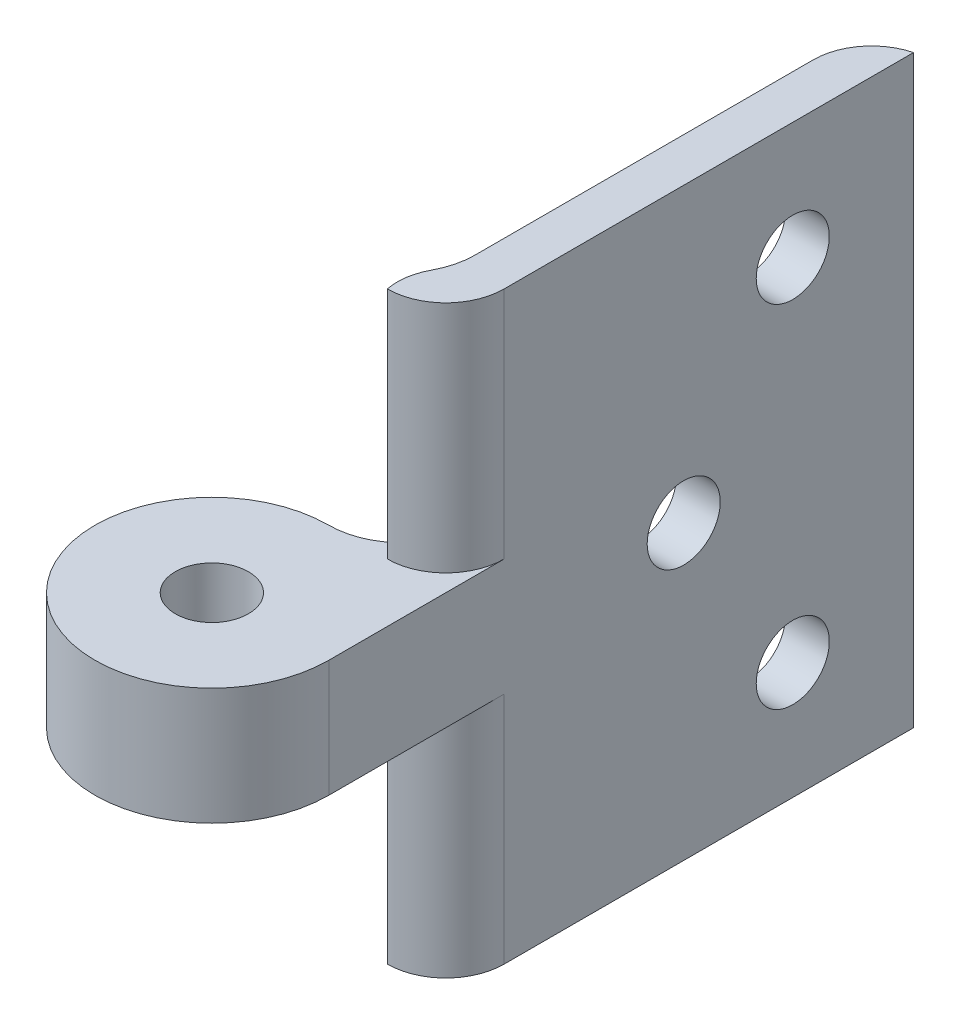
SolidWorks part; units mm, degrees
ref_plane "Front Plane" through (0, 0, 0) normal (0, 0, 1) x (1, 0, 0)
ref_plane "Top Plane" through (0, 0, 0) normal (0, 1, 0) x (1, 0, 0)
ref_plane "Right Plane" through (0, 0, 0) normal (1, 0, 0) x (0, 0, -1)
sketch "Sketch1" plane through (0, 0, 0) normal (0, 1, 0) x (1, 0, 0)
  line L0 (4, 0) -> (4, 20)
  line L1 (2.5, 6.5) -> (2.5, 15.12)
  line L5 (2.5, 15.12) -> (2.5, 20)
  line L6 (2.5, 20) -> (4, 20)
  circle A0 centre (0, 0) radius 1.25
  arc A1 (0, 4) -> (4, 0) centre (0, 0) ccw
  arc A2 (2.5, 6.5) -> (0, 4) centre (0, 6.5) cw
  dimension "D1" = 2.5
  dimension "D2" = 8
  dimension "D4" = 2.5
  dimension "D3" = 20
extrude "Boss-Extrude1" add sketch "Sketch1" along normal blind 20
sketch "Sketch2" plane through (2.5, 0, 0) normal (-1, 0, 0) x (0, 0, 1)
  line L0 (-6.5, 20) -> (-6.5, 0) construction
  circle A0 centre (-12.1392, 10) radius 1.25
  circle A1 centre (-15.8687, 4) radius 1.25
  circle A2 centre (-15.8687, 16) radius 1.25
  point P11 (-6.5, 10)
  dimension "D1" = 2.5
extrude "Cut-Extrude1" cut sketch "Sketch2" against normal through all both and the other way through all
sketch "Sketch3" plane through (0, 0, 0) normal (1, 0, 0) x (0, 0, -1)
  line L0 (4, 20) -> (4, 0) construction
  line L11 (-6, 0) -> (4, 0)
  line L15 (-6, 0) -> (-6, 8)
  line L16 (-6, 8) -> (4, 8)
  line L17 (4, 0) -> (4, 8)
  line L20 (-6, 0) -> (4, 8) construction
  line L21 (-6, 8) -> (4, 0) construction
  line L22 (4, 12) -> (-5.3571, 12)
  line L23 (4, 12) -> (4, 20)
  line L24 (4, 20) -> (-5.3571, 20)
  line L25 (-5.3571, 12) -> (-5.3571, 20)
  line L26 (4, 12) -> (-5.3571, 20) construction
  line L27 (4, 20) -> (-5.3571, 12) construction
  line L28 (-4, 0) -> (4, 0) construction
  line L29 (4, 20) -> (-4, 20) construction
  point P0 (-1.0127, 3.8091)
  point P2 (-0.5182, 16.1371)
  dimension "D1" = 4
  dimension "D2" = 8
  dimension "D3" = 10
extrude "Cut-Extrude3" cut sketch "Sketch3" against normal through all both and the other way through all
fillet "Fillet3" radius 2 1 edges at (4, 16, -4)
fillet "Fillet4" radius 2 1 edges at (0, 16, -4)
fillet "Fillet8" radius 2 1 edges at (4, 4, -4)
fillet "Fillet9" radius 2 1 edges at (0, 4, -4)
fillet "Fillet11" radius 2 1 edges at (2.5, 10, -20)
